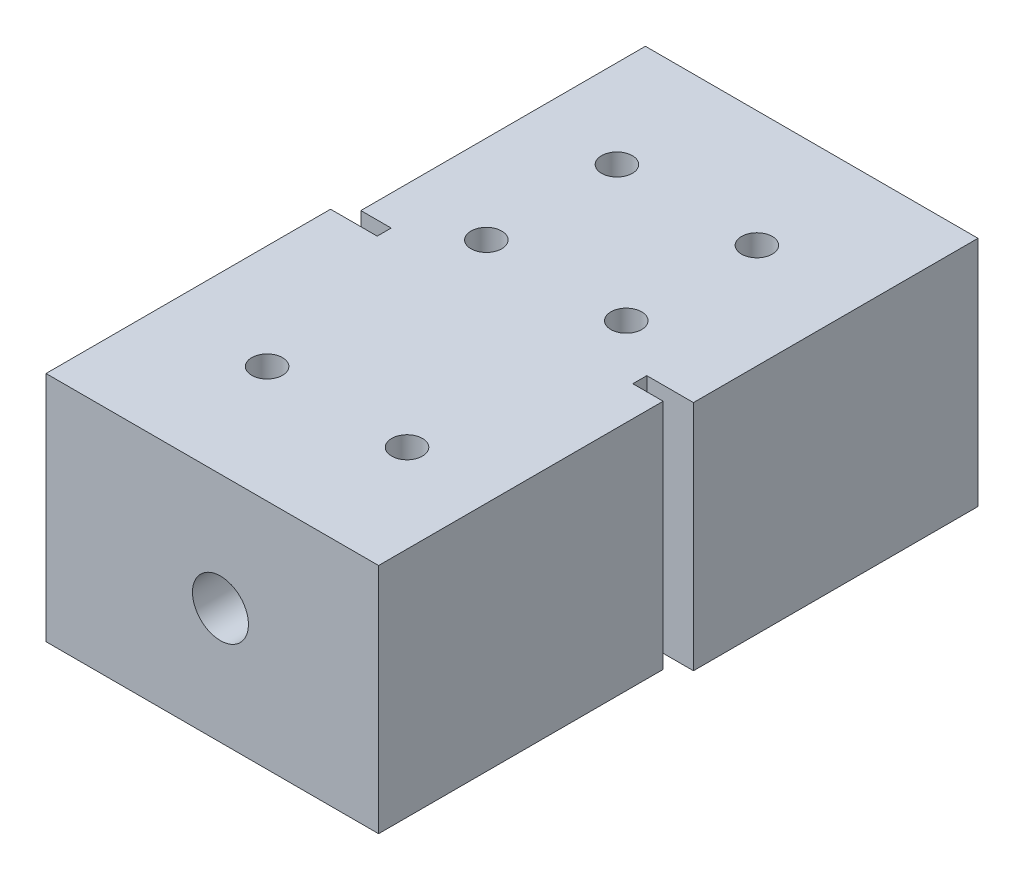
SolidWorks part; units mm, degrees
material "Beech"
ref_plane "Front Plane" through (0, 0, 0) normal (0, 0, 1) x (1, 0, 0)
ref_plane "Top Plane" through (0, 0, 0) normal (0, 1, 0) x (1, 0, 0)
ref_plane "Right Plane" through (0, 0, 0) normal (1, 0, 0) x (0, 0, -1)
sketch "Sketch1" plane through (0, 0, 0) normal (0, 0, 1) x (1, 0, 0)
  line L1 (0, 0) -> (74.8, 0)
  line L2 (0, 0) -> (0, 49.8)
  line L3 (0, 49.8) -> (74.8, 49.8)
  line L4 (74.8, 0) -> (74.8, 49.8)
  dimension "D1" = 74.8
  dimension "D2" = 49.8
extrude "slider body" add sketch "Sketch1" along normal blind 125
sketch "Sketch2" plane through (0, 0, 0) normal (0, 0, -1) x (-1, 0, 0)
  line L0 (-74.8, 49.8) -> (0, 0) construction
  line L1 (-74.8, 0) -> (0, 49.8) construction
  circle A0 centre (-37.4, 24.9) radius 11
  dimension "D1" = 22
extrude "lead nut inset" cut sketch "Sketch2" against normal blind 15
sketch "Sketch3" plane through (0, 0, 15) normal (0, 0, -1) x (-1, 0, 0)
  circle A0 centre (-37.4, 24.9) radius 6
  circle A1 centre (-37.4, 24.9) radius 11 construction
  dimension "D1" = 12
extrude "leadscrew clearance" cut sketch "Sketch3" against normal through all
sketch "Sketch9" plane through (0, 0, 0) normal (0, -1, 0) x (1, 0, 0)
  line L0 (74.8, 125) -> (74.8, 0) construction
  line L1 (74.8, 64) -> (64.8, 64)
  line L2 (74.8, 64) -> (74.8, 61)
  line L3 (74.8, 61) -> (64.8, 61)
  line L4 (64.8, 64) -> (64.8, 61)
  point P6 (74.8, 62.5)
  point P7 (74.8, 62.5)
  dimension "D1" = 10
  dimension "D2" = 3
extrude "decoupling slit" cut sketch "Sketch9" against normal through all
hole_wizard "bolt clearance holes" positions "Sketch4" profile "Sketch6" hole size "M6" standard "ANSI Metric" end condition through all
sketch "Sketch4" plane through (0, 49.8, 0) normal (0, 1, 0) x (1, 0, 0)
  line L1 (52.4, -100) -> (22.4, -100)
  line L2 (52.4, -100) -> (52.4, -25)
  line L3 (52.4, -25) -> (22.4, -25)
  line L4 (22.4, -100) -> (22.4, -25)
  line L10 (22.4, -62.5) -> (0, -62.5)
  line L11 (0, -125) -> (0, 0) construction
  line L13 (37.4, -100) -> (37.4, -125)
  line L14 (74.8, -125) -> (0, -125) construction
  point P1 (52.4, -100)
  point P2 (22.4, -25)
  point P47 (52.4, -25)
  point P48 (22.4, -100)
  point P72 (22.4, -53)
  point P74 (52.4, -53)
  dimension "D1" = 30
  dimension "D2" = 75
  dimension "D3" = 28
sketch "Sketch6" plane through (52.4, 49.8, 100) normal (1, 0, 0) x (0, 0, 1)
  line L0 (0, 0) -> (0, 49.8)
  line L1 (0, 49.8) -> (3.3, 49.8)
  line L2 (3.3, 49.8) -> (3.3, 0)
  line L5 (3.3, 0) -> (0, 0)
  line L11 (0, -6.35) -> (0, 107.95) construction
  dimension "Thru Hole Dia." = 6.6
  dimension "Thru Hole Depth" = 49.8
sketch "Sketch7" plane through (0, 0, 0) normal (0, -1, 0) x (1, 0, 0)
  circle A0 centre (22.4, 100) radius 6
  circle A1 centre (52.4, 100) radius 6
  circle A2 centre (52.4, 25) radius 6
  circle A3 centre (22.4, 25) radius 6
  dimension "D1" = 12
extrude "nut clearance counterbores" [suppressed] cut sketch "Sketch7" against normal blind 10
ref_plane "midplane along length" through (37.4, 0, 0) normal (-1, 0, 0) x (0, 0, 1)
mirror "mirror slit" about plane through (37.4, 0, 0) normal (-1, 0, 0) of "decoupling slit"
sketch "Sketch10" plane through (0, 0, 0) normal (0, -1, 0) x (1, 0, 0)
  line L0 (74.8, 64) -> (64.8, 64) construction
  line L1 (74.8, 125) -> (71.3, 125)
  line L2 (74.8, 125) -> (74.8, 64)
  line L3 (74.8, 64) -> (71.3, 64)
  line L4 (71.3, 125) -> (71.3, 64)
  line L5 (0, 0) -> (74.8, 0) construction
  line L6 (0, 61) -> (3.5, 61)
  line L7 (0, 61) -> (0, 0)
  line L8 (0, 0) -> (3.5, 0)
  line L9 (3.5, 61) -> (3.5, 0)
  dimension "D1" = 3.5
extrude "neoprene inlay" cut sketch "Sketch10" against normal through all
equation "\"board_thickness\" = 18mm"
equation "\"way_width\"= 75mm"
equation "\"way_thickness\"= 50mm"
equation "\"radial_clearance\"= 0.1mm"
equation "\"slider_width\"= \"way_width\"-2* \"radial_clearance\""
equation "\"slider_thickness\" = \"way_thickness\" - 2 * \"radial_clearance\""
equation "\"column_width\"= \"way_width\" + 2 * \"board_thickness\""
equation "\"boxway_slot_width\" = 50mm"
equation "\"keeper_rail_width\" = (\"column_width\" - \"boxway_slot_width\")/2"
equation "\"slider_length\" = 125mm"
equation "\"D1@Sketch1\"=\"slider_width\""
equation "\"D2@Sketch1\"=\"slider_thickness\""
equation "\"D1@slider body\" = \"slider_length\""
equation "\"nut_diameter\"= 22mm"
equation "\"nut_length\"= 15mm"
equation "\"D1@Sketch2\"=\"nut_diameter\""
equation "\"D1@lead nut inset\" = \"nut_length\""
equation "\"leadscrew_diameter\"= 10mm"
equation "\"leadscrew_radial_clearance\"= 1mm"
equation "\"D1@Sketch3\"=\"leadscrew_diameter\"+2* \"leadscrew_radial_clearance\""
equation "\"bearing_bolt_pattern_width\" = 30mm"
equation "\"bearing_bolt_pattern_height\" = 75mm"
equation "\"desktop_bolt_pattern_width\" = 30mm"
equation "\"desktop_bolt_pattern_height\" = 30mm"
equation "\"D1@Sketch4\"=\"bearing_bolt_pattern_width\""
equation "\"D2@Sketch4\"=\"bearing_bolt_pattern_height\""
equation "\"bearing_bolt_nut_counterbore_diameter\" = 12mm"
equation "\"bearing_bolt_nut_counterbore_depth\"= 10mm"
equation "\"D1@Sketch7\"=\"bearing_bolt_nut_counterbore_diameter\""
equation "\"D1@nut clearance counterbores\" = \"bearing_bolt_nut_counterbore_depth\""
